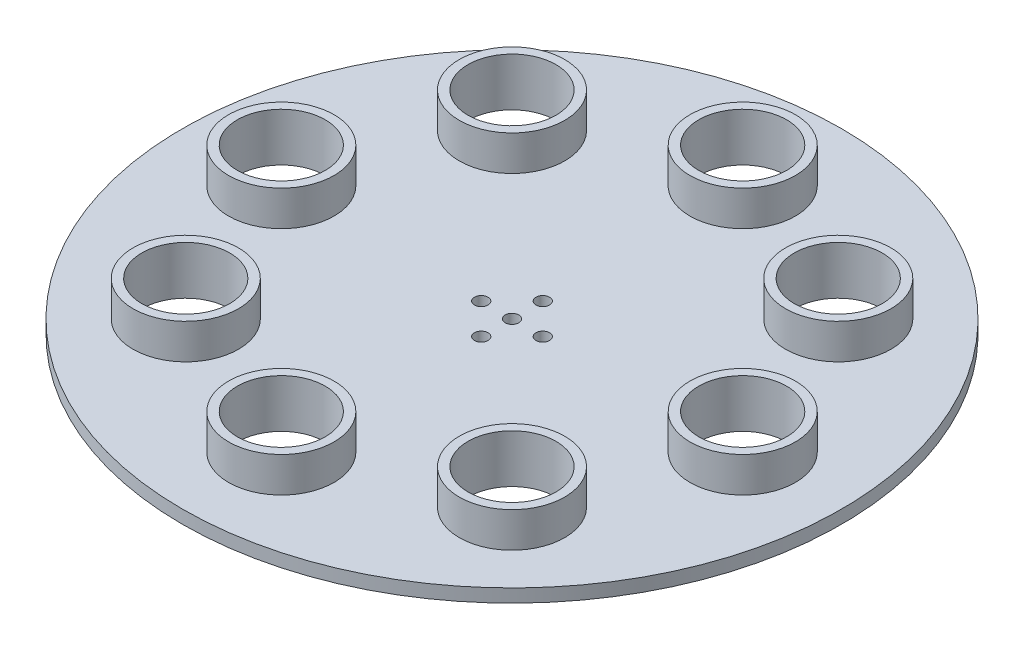
SolidWorks part; units mm, degrees
ref_plane "前视基准面" through (0, 0, 0) normal (0, 0, 1) x (1, 0, 0)
ref_plane "上视基准面" through (0, 0, 0) normal (0, 1, 0) x (1, 0, 0)
ref_plane "右视基准面" through (0, 0, 0) normal (1, 0, 0) x (0, 0, -1)
other "Configuration Table"
sketch "草图1" plane through (0, 0, 0) normal (0, 1, 0) x (1, 0, 0)
  line L0 (0, 0) -> (100.63, 0) construction
  line L1 (0, 0) -> (0, -63) construction
  line L2 (0, 0) -> (44.5477, -44.5477) construction
  line L3 (-37.1231, -37.1231) -> (51.9723, 51.9723) construction
  circle A0 centre (0, 0) radius 75
  circle A3 centre (0, 52.5) radius 10
  circle A4 centre (-52.5, 0) radius 10
  circle A5 centre (0, -52.5) radius 10
  circle A6 centre (52.5, 0) radius 10
  circle A7 centre (-37.1231, 37.1231) radius 10
  circle A8 centre (-37.1231, -37.1231) radius 10
  circle A9 centre (37.1231, 37.1231) radius 10
  circle A10 centre (37.1231, -37.1231) radius 10
  circle A11 centre (0, 0) radius 1.55
  circle A12 centre (0, 7) radius 1.55
  circle A13 centre (7, 0) radius 1.55
  circle A14 centre (-7, 0) radius 1.55
  circle A15 centre (0, -7) radius 1.55
  circle A16 centre (-37.1231, 37.1231) radius 12
  circle A17 centre (0, 52.5) radius 12
  circle A18 centre (37.1231, 37.1231) radius 12
  circle A19 centre (52.5, 0) radius 12
  circle A20 centre (37.1231, -37.1231) radius 12
  circle A21 centre (0, -52.5) radius 12
  circle A22 centre (-37.1231, -37.1231) radius 12
  circle A23 centre (-52.5, 0) radius 12
  point P18 (33.5849, 33.5849)
  point P20 (-52.5, 0)
  point P21 (0, 52.5)
  point P47 (0, 0)
  point P48 (0, 0)
  point P49 (0, 0)
  point P50 (0, 0)
  point P51 (0, 0)
  point P52 (0, 0)
  point P53 (0, 0)
sketch "草图2" plane through (0, 0, 0) normal (0, 1, 0) x (1, 0, 0)
sketch "草图3" plane through (0, 0, 0) normal (0, 1, 0) x (1, 0, 0)
sketch "草图4" plane through (0, 0, 0) normal (0, 1, 0) x (1, 0, 0)
extrude "凸台-拉伸2" add sketch "草图1" along normal blind 11 contours A23 A4 | A22 A8 | A21 A5 | A20 A10 | A19 A6 | A17 A3 | A18 A9 | A16 A7 region at (-48.7837, 0, -37.1231) region at (-11.6606, 0, -52.5) region at (25.4625, 0, -37.1231) region at (40.8394, 0, 0) region at (25.4625, 0, 37.1231) region at (-11.6606, 0, 52.5) region at (-48.7837, 0, 37.1231) region at (-64.1606, 0, 0)
extrude "凸台-拉伸3" add sketch "草图1<8>" along normal blind 3 contours A0 A23 A22 A21 A20 A19 A18 A17 A16 A15 A14 A13 A12 A11 region at (-72.8787, 0, 0)
sketch "草图1<8>" plane through (0, 0, 0) normal (0, 1, 0) x (1, 0, 0) same geometry as "草图1"
